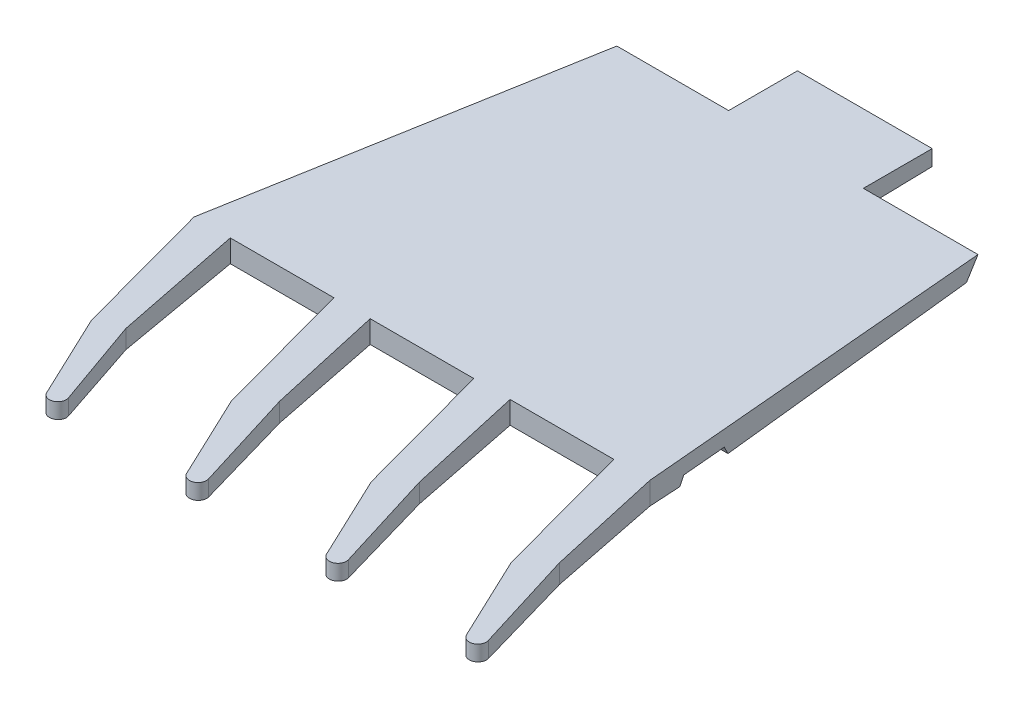
SolidWorks part; units mm, degrees
note: The reader was unsure of these and kept them because the rebuilt part matched: shared geometry of "Sketch4<2>".
ref_plane "Front Plane" through (0, 0, 0) normal (0, 0, 1) x (1, 0, 0)
ref_plane "Top Plane" through (0, 0, 0) normal (0, 1, 0) x (1, 0, 0)
ref_plane "Right Plane" through (0, 0, 0) normal (1, 0, 0) x (0, 0, -1)
sketch "Sketch1" plane through (0, 0, 0) normal (0, 1, 0) x (1, 0, 0)
  line L0 (-28, 0) -> (71.5794, 0) construction
  line L5 (0, 0) -> (0, 69.1076) construction
  line L27 (71.5794, -31.8551) -> (65.0609, -17.4055) construction
  line L30 (-28, 2.3596) -> (-28, -31.8551) construction
  line L60 (0, 69.1076) -> (0, -57.2153) construction
  line L62 (-28, 69.1076) -> (71.5794, 69.1076) construction
  line L63 (-28, 69.1076) -> (-28, -57.2153) construction
  line L64 (-28, -57.2153) -> (71.5794, -57.2153) construction
  line L65 (71.5794, 69.1076) -> (71.5794, -57.2153) construction
sketch "Sketch2" plane through (0, 0, 0) normal (1, 0, 0) x (0, 0, -1)
  line L0 (2.9339, -4.509) -> (69.1418, -3.0028) construction
  line L1 (69.1076, 0) -> (69.1418, -3.0028) construction
  line L2 (69.1076, 0) -> (-57.2153, 0) construction
  line L7 (-7.216, -4.5075) -> (-57.2158, -3) construction
  line L8 (-7.216, -4.5075) -> (-6.4274, -3.0076) construction
  line L9 (2.1457, -3.0089) -> (-6.4274, -3.0076) construction
  line L10 (2.1457, -3.0089) -> (2.9339, -4.509) construction
  line L11 (2.9339, -4.509) -> (69.1418, -3.0028)
  line L12 (69.1076, 0) -> (69.1418, -3.0028)
  line L13 (69.1076, 0) -> (-58.6475, 0)
  line L14 (-58.6475, 0) -> (-58.6475, -2.9568)
  line L18 (-7.216, -4.5075) -> (-58.6475, -2.9568)
  line L19 (-7.216, -4.5075) -> (-6.4274, -3.0076)
  line L20 (2.1457, -3.0089) -> (-6.4274, -3.0076)
  line L21 (2.1457, -3.0089) -> (2.9339, -4.509)
  line L22 (67.6061, -1.5187) -> (-57.2156, -1.5) construction
  line L23 (67.6061, -1.5187) -> (-58.6475, -1.4998) construction
extrude "Boss-Extrude1" add sketch "Sketch2" along normal up to vertex (71.5794 mm away) from vertex at -28 starting at point (-28, 0, 57.2153)
sketch "Sketch3" plane through (0, 0, 0) normal (0, 1, 0) x (1, 0, 0)
  line L0 (-28, -13.5555) -> (-20.6376, -40.7086) construction
  line L1 (-20.6376, -40.7086) -> (-12.1395, -58.6475) construction
  line L2 (-12.1395, -58.6475) -> (-9.4206, -57.2153) construction
  line L3 (-9.4206, -57.2153) -> (-15.9391, -38.7769) construction
  line L4 (-15.9391, -38.7769) -> (-21, -13.5555) construction
  line L5 (-21, -13.5555) -> (-1, -13.5555) construction
  line L6 (-1, -13.5555) -> (6.3624, -40.7086) construction
  line L7 (6.3624, -40.7086) -> (14.8605, -58.6475) construction
  line L8 (14.8605, -58.6475) -> (17.5794, -57.2153) construction
  line L9 (17.5794, -57.2153) -> (11.0609, -36.1015) construction
  line L10 (11.0609, -36.1015) -> (6, -13.5555) construction
  line L11 (26, -13.5555) -> (6, -13.5555) construction
  line L12 (26, -13.5555) -> (33.3624, -40.7086) construction
  line L13 (33.3624, -40.7086) -> (41.8605, -58.6475) construction
  line L14 (41.8605, -58.6475) -> (44.5794, -57.2153) construction
  line L15 (44.5794, -57.2153) -> (38.0609, -36.1015) construction
  line L16 (38.0609, -36.1015) -> (33, -13.5555) construction
  line L17 (33, -13.5555) -> (53, -13.5555) construction
  line L18 (53, -13.5555) -> (60.3624, -40.7086) construction
  line L19 (60.3624, -40.7086) -> (68.8605, -58.6475) construction
  line L20 (68.8605, -58.6475) -> (71.5794, -57.2153) construction
  line L21 (71.5794, -57.2153) -> (65.0609, -36.1015) construction
  line L22 (65.0609, -36.1015) -> (60, -13.5555) construction
  line L23 (-28, -13.5555) -> (-20.6376, -40.7086)
  line L24 (-20.6376, -40.7086) -> (-12.1395, -58.6475) construction
  line L25 (-12.1395, -58.6475) -> (-9.4206, -57.2153) construction
  line L26 (-9.4206, -57.2153) -> (-15.9391, -38.7769) construction
  line L27 (-15.9391, -38.7769) -> (-21, -13.5555)
  line L28 (-21, -13.5555) -> (-1, -13.5555)
  line L29 (-1, -13.5555) -> (6.3624, -40.7086)
  line L30 (6.3624, -40.7086) -> (14.8605, -58.6475) construction
  line L31 (14.8605, -58.6475) -> (17.5794, -57.2153) construction
  line L32 (17.5794, -57.2153) -> (11.0609, -36.1015) construction
  line L33 (11.0609, -36.1015) -> (6, -13.5555)
  line L34 (26, -13.5555) -> (6, -13.5555)
  line L35 (26, -13.5555) -> (33.3624, -40.7086)
  line L36 (33.3624, -40.7086) -> (41.8605, -58.6475) construction
  line L37 (41.8605, -58.6475) -> (44.5794, -57.2153) construction
  line L38 (44.5794, -57.2153) -> (38.0609, -36.1015) construction
  line L39 (38.0609, -36.1015) -> (33, -13.5555)
  line L40 (33, -13.5555) -> (53, -13.5555)
  line L41 (53, -13.5555) -> (60.3624, -40.7086)
  line L42 (60.3624, -40.7086) -> (68.8605, -58.6475) construction
  line L43 (68.8605, -58.6475) -> (71.5794, -57.2153) construction
  line L44 (71.5794, -57.2153) -> (65.0609, -36.1015) construction
  line L45 (65.0609, -36.1015) -> (60, -13.5555)
  line L46 (-28, -13.5555) -> (-13.4243, 69.1076)
  line L47 (-13.4243, 69.1076) -> (52.7679, 69.1076)
  line L48 (52.7679, 69.1076) -> (60, -13.5555)
  line L49 (-28, 69.1076) -> (71.5794, 69.1076) construction
  line L50 (-12.859, -57.1288) -> (-20.6376, -40.7086)
  line L51 (-15.9391, -38.7769) -> (-9.8848, -55.9024)
  line L52 (14.1277, -57.1007) -> (6.3624, -40.7086)
  line L53 (11.0609, -36.1015) -> (17.1778, -55.9145)
  line L54 (33.3624, -40.7086) -> (41.1277, -57.1007)
  line L55 (44.1778, -55.9145) -> (38.0609, -36.1015)
  line L56 (60.3624, -40.7086) -> (68.1277, -57.1007)
  line L57 (71.1778, -55.9145) -> (65.0609, -36.1015)
  arc A0 (71.1778, -55.9145) -> (68.1277, -57.1007) centre (69.6103, -56.3984) cw
  arc A1 (44.1778, -55.9145) -> (41.1277, -57.1007) centre (42.6103, -56.3984) cw
  arc A2 (17.1778, -55.9145) -> (14.1277, -57.1007) centre (15.6103, -56.3984) cw
  arc A3 (-9.8848, -55.9024) -> (-12.859, -57.1288) centre (-11.4034, -56.4393) cw
  dimension "D1" = 100
  dimension "D2" = 95
extrude "Cut-Extrude1" cut sketch "Sketch3" against normal through all flip side to cut
sketch "Sketch4" plane through (0, 0, 0) normal (1, 0, 0) x (0, 0, -1)
  line L0 (23.9166, -44.4449) -> (59.292, 4.2751) construction
  line L1 (23.9166, -44.4449) -> (59.292, 4.2751) construction
  line L2 (53.3763, -3.3615) -> (55.8171, 0)
  line L3 (55.8171, 0) -> (69.1076, 0)
  line L4 (69.1076, 0) -> (69.1418, -3.0028)
  line L5 (69.1418, -3.0028) -> (53.3763, -3.3615)
  line L8 (69.1076, 0) -> (69.1418, -3.0028) construction
  line L9 (69.1076, 0) -> (-57.2153, 0) construction
  line L10 (2.9339, -4.509) -> (69.1418, -3.0028) construction
  dimension "D1" = 0.3
extrude "Cut-Extrude2" cut sketch "Sketch4" against normal through all from vertex at 5.8036
extrude "Cut-Extrude3" cut sketch "Sketch4<2>" along normal through all from vertex at 31.8036
sketch "Sketch4<2>" plane through (0, 0, 0) normal (1, 0, 0) x (0, 0, -1) same geometry as "Sketch4"
